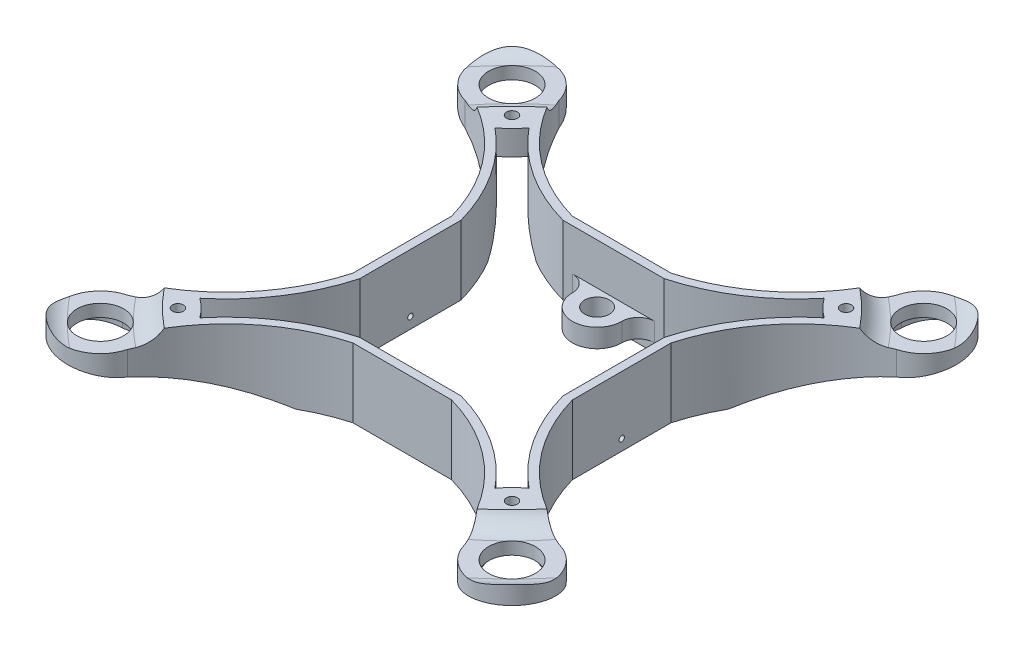
SolidWorks part; units mm, degrees
ref_plane "前视基准面" through (0, 0, 0) normal (0, 0, 1) x (1, 0, 0)
ref_plane "上视基准面" through (0, 0, 0) normal (0, 1, 0) x (1, 0, 0)
ref_plane "右视基准面" through (0, 0, 0) normal (1, 0, 0) x (0, 0, -1)
other "Configuration Table"
sketch "草图1" plane through (0, 0, 0) normal (0, 1, 0) x (1, 0, 0)
  line L5 (0, 0) -> (0, 44.9751) construction
  line L6 (0, 0) -> (70.3085, 0) construction
  line L11 (-18.5, 9.2045) -> (-18.5, -9.2045)
  line L17 (-20, -20) -> (20, 20) construction
  line L18 (-20, 20) -> (20, -20) construction
  line L23 (-37.5, -37.5) -> (37.5, 37.5) construction
  line L24 (-37.5, 37.5) -> (37.5, -37.5) construction
  line L25 (-9.2045, 18.5) -> (9.2045, 18.5)
  line L26 (-37.5, -37.5) -> (-32.5503, -32.5503)
  line L27 (-20, 9) -> (-20, -9)
  line L28 (0, 0) -> (32.5503, 32.5503)
  line L29 (18.5, 9.2045) -> (18.5, -9.2045)
  line L30 (9, -20) -> (-9, -20)
  line L31 (9.2045, -18.5) -> (-9.2045, -18.5)
  line L32 (20, 9) -> (20, -9)
  line L33 (-9, 20) -> (9, 20)
  arc A33 (-39.3117, -30.7385) -> (-30.7385, -39.3117) centre (-37.5, -37.5) ccw
  arc A34 (-30.7385, 39.3117) -> (-39.3117, 30.7385) centre (-37.5, 37.5) ccw
  circle A35 centre (-37.5, 37.5) radius 4.25
  circle A36 centre (37.5, 37.5) radius 4.25
  circle A37 centre (37.5, -37.5) radius 4.25
  circle A38 centre (-37.5, -37.5) radius 4.25
  arc A45 (30.7385, -39.3117) -> (39.3117, -30.7385) centre (37.5, -37.5) ccw
  arc A46 (39.3117, 30.7385) -> (30.7385, 39.3117) centre (37.5, 37.5) ccw
  arc A48 (-20, 9) -> (-39.3117, 30.7385) centre (-52.022, 0) ccw
  arc A51 (-39.3117, -30.7385) -> (-20, -9) centre (-52.022, 0) ccw
  arc A52 (-30.7385, 39.3117) -> (-9, 20) centre (0, 52.022) ccw
  arc A53 (9, 20) -> (30.7385, 39.3117) centre (0, 52.022) ccw
  arc A54 (20, -9) -> (39.3117, -30.7385) centre (52.022, 0) ccw
  arc A55 (39.3117, 30.7385) -> (20, 9) centre (52.022, 0) ccw
  arc A58 (30.7385, -39.3117) -> (9, -20) centre (0, -52.022) ccw
  arc A59 (-9, -20) -> (-30.7385, -39.3117) centre (0, -52.022) ccw
  arc A60 (-38.8355, -32.1646) -> (-18.5, -9.2045) centre (-52.022, 0) ccw
  arc A61 (-18.5, 9.2045) -> (-38.8355, 32.1646) centre (-52.022, 0) ccw
  arc A62 (-32.1646, 38.8355) -> (-38.8355, 32.1646) centre (-37.5, 37.5) ccw
  arc A63 (-32.1646, 38.8355) -> (-9.2045, 18.5) centre (0, 52.022) ccw
  arc A64 (9.2045, 18.5) -> (32.1646, 38.8355) centre (0, 52.022) ccw
  arc A65 (38.8355, 32.1646) -> (32.1646, 38.8355) centre (37.5, 37.5) ccw
  arc A66 (38.8355, 32.1646) -> (18.5, 9.2045) centre (52.022, 0) ccw
  arc A67 (18.5, -9.2045) -> (38.8355, -32.1646) centre (52.022, 0) ccw
  arc A68 (32.1646, -38.8355) -> (38.8355, -32.1646) centre (37.5, -37.5) ccw
  arc A69 (32.1646, -38.8355) -> (9.2045, -18.5) centre (0, -52.022) ccw
  arc A70 (-9.2045, -18.5) -> (-32.1646, -38.8355) centre (0, -52.022) ccw
  arc A71 (-38.8355, -32.1646) -> (-32.1646, -38.8355) centre (-37.5, -37.5) ccw
  point P3 (0, 0)
  point P9 (0, 0)
  dimension "D1" = 1.5
extrude "凸台-拉伸1" add sketch "草图1" along normal blind 12.6 contours A59 L30 A58 A45 A54 L32 A55 A46 A53 L33 A52 A34 A48 L27 A51 A33 A71 A60 L11 A61 A62 A63 L25 A64 A65 A66 L29 A67 A68 A69 L31 A70
sketch "草图3" plane through (0, 0, 0) normal (0, -1, 0) x (1, 0, 0)
  line L0 (-37.5, 37.5) -> (37.5, -37.5) construction
  line L2 (37.5, 37.5) -> (-37.5, -37.5) construction
ref_plane "基准面1" through (0, 0, 0) normal (0.7071, 0, -0.7071) x (-0.7071, 0, -0.7071)
ref_plane "基准面2" through (0, 0, 0) normal (-0.7071, 0, -0.7071) x (-0.7071, 0, 0.7071)
sketch "草图6" plane through (0, 12.6, 0) normal (0, 1, 0) x (1, 0, 0)
  line L0 (-37.5, 37.5) -> (-30.4289, 30.4289)
  line L1 (37.5, -37.5) -> (-37.5, 37.5) construction
  line L2 (-37.5, -37.5) -> (-30.4289, -30.4289)
  line L3 (-37.5, -37.5) -> (37.5, 37.5) construction
  line L4 (37.5, -37.5) -> (30.4289, -30.4289)
  line L5 (37.5, 37.5) -> (30.4289, 30.4289)
  arc A0 (-30.7385, 39.3117) -> (-39.3117, 30.7385) centre (-37.5, 37.5) ccw
  circle A1 centre (-37.5, 37.5) radius 4.25
  arc A2 (39.3117, 30.7385) -> (30.7385, 39.3117) centre (37.5, 37.5) ccw
  circle A3 centre (37.5, 37.5) radius 4.25
  arc A4 (30.7385, -39.3117) -> (39.3117, -30.7385) centre (37.5, -37.5) ccw
  circle A5 centre (37.5, -37.5) radius 4.25
  arc A6 (-39.3117, -30.7385) -> (-30.7385, -39.3117) centre (-37.5, -37.5) ccw
  circle A7 centre (-37.5, -37.5) radius 4.25
  circle A8 centre (-30.4289, 30.4289) radius 1
  arc A9 (-31.3407, 26.0517) -> (-26.0517, 31.3407) centre (-37.5, 37.5) ccw
  arc A10 (26.0517, 31.3407) -> (31.3407, 26.0517) centre (37.5, 37.5) ccw
  arc A11 (31.3407, -26.0517) -> (26.0517, -31.3407) centre (37.5, -37.5) ccw
  arc A12 (-26.0517, -31.3407) -> (-31.3407, -26.0517) centre (-37.5, -37.5) ccw
  circle A13 centre (-30.4289, -30.4289) radius 1
  circle A14 centre (30.4289, -30.4289) radius 1
  circle A15 centre (30.4289, 30.4289) radius 1
  arc A16 (20, -9) -> (39.3117, -30.7385) centre (52.022, 0) ccw construction
  arc A17 (30.7385, -39.3117) -> (9, -20) centre (0, -52.022) ccw construction
  arc A18 (-9, -20) -> (-30.7385, -39.3117) centre (0, -52.022) ccw construction
  arc A19 (-39.3117, -30.7385) -> (-20, -9) centre (-52.022, 0) ccw construction
  arc A20 (39.3117, 30.7385) -> (20, 9) centre (52.022, 0) ccw construction
  arc A21 (9, 20) -> (30.7385, 39.3117) centre (0, 52.022) ccw construction
  arc A22 (-20, 9) -> (-39.3117, 30.7385) centre (-52.022, 0) ccw construction
  arc A23 (-30.7385, 39.3117) -> (-9, 20) centre (0, 52.022) ccw construction
  arc A24 (31.3407, -26.0517) -> (39.3117, -30.7385) centre (52.022, 0) ccw
  arc A25 (30.7385, -39.3117) -> (26.0517, -31.3407) centre (0, -52.022) ccw
  arc A26 (-26.0517, -31.3407) -> (-30.7385, -39.3117) centre (0, -52.022) ccw
  arc A27 (-39.3117, -30.7385) -> (-31.3407, -26.0517) centre (-52.022, 0) ccw
  arc A28 (39.3117, 30.7385) -> (31.3407, 26.0517) centre (52.022, 0) ccw
  arc A29 (26.0517, 31.3407) -> (30.7385, 39.3117) centre (0, 52.022) ccw
  arc A30 (-31.3407, 26.0517) -> (-39.3117, 30.7385) centre (-52.022, 0) ccw
  arc A31 (-30.7385, 39.3117) -> (-26.0517, 31.3407) centre (0, 52.022) ccw
extrude "凸台-拉伸2" add sketch "草图6" against normal blind 4.5
sketch "草图4" plane through (0, 0, 0) normal (-0.7071, 0, -0.7071) x (-0.7071, 0, 0.7071)
  line L0 (0, 0) -> (0, 41.1063) construction
  line L2 (-49.533, 12.6) -> (-60.033, 12.6) construction
  line L3 (-53.033, 12.6) -> (-61.033, 12.6)
  line L4 (-53.033, 12.6) -> (-45.033, 12.6)
  line L6 (-53.033, 10.35) -> (-48.783, 10.35)
  line L7 (-53.033, 10.35) -> (-57.283, 10.35)
  arc A1 (-61.033, 12.6) -> (-56.783, 10.35) centre (-57.033, 15.0167) ccw
  arc A2 (-49.283, 10.35) -> (-45.033, 12.6) centre (-49.033, 15.0167) ccw
revolve "切除-旋转1" cut sketch "草图4" angle 360 about L0
sketch "草图7" plane through (0, 0, 0) normal (0.7071, 0, -0.7071) x (-0.7071, 0, -0.7071)
  line L0 (0, 0) -> (0, 23.5599) construction
  line L6 (-53.033, 0) -> (-60.033, 0)
  line L7 (-60.033, 0) -> (-60.033, 8.1)
  line L8 (-53.033, 0) -> (-28.28, 0)
  arc A1 (-28.28, 0) -> (-60.033, 8.1) centre (-104.9845, -234.4035) ccw
revolve "切除-旋转6" cut sketch "草图7" angle 360 about L0
sketch "草图10" plane through (0, 0, 0) normal (0, -1, 0) x (1, 0, 0)
  line L0 (18.5, 9.2045) -> (18.5, -9.2045) construction
  line L1 (20, -9) -> (20, 9) construction
  line L2 (-9, -20) -> (9, -20) construction
  line L4 (-18.5, -9.2045) -> (-18.5, 9.2045) construction
  line L5 (-20, 9) -> (-20, -9) construction
  line L6 (-9.2045, 18.5) -> (9.2045, 18.5) construction
  line L7 (9, 20) -> (-9, 20) construction
  line L8 (18.5, 9.2045) -> (18.5, -9.2045)
  line L9 (20, -9) -> (20, 9)
  line L10 (-9, -20) -> (9, -20)
  line L12 (-18.5, -9.2045) -> (-18.5, 9.2045)
  line L13 (-20, 9) -> (-20, -9)
  line L14 (-9.2045, 18.5) -> (9.2045, 18.5)
  line L15 (9, 20) -> (-9, 20)
  line L21 (0, -18.5) -> (4.5, -18.5)
  line L22 (0, -18.5) -> (-4.5, -18.5)
  line L23 (-4.5, -18.5) -> (-4.5, -15.5)
  line L24 (4.5, -18.5) -> (4.5, -15.5)
  arc A1 (22.083, 17.6664) -> (18.5, 9.2045) centre (52.022, 0) ccw construction
  arc A2 (18.5, -9.2045) -> (22.083, -17.6664) centre (52.022, 0) ccw construction
  arc A3 (4.5, -15.5) -> (-4.5, -15.5) centre (0, -15.5) ccw
  arc A4 (20, -9) -> (23.0637, -16.3653) centre (52.022, 0) ccw construction
  arc A5 (23.0637, 16.3653) -> (20, 9) centre (52.022, 0) ccw construction
  arc A7 (-9, -20) -> (-16.3653, -23.0637) centre (0, -52.022) ccw construction
  arc A8 (16.3653, -23.0637) -> (9, -20) centre (0, -52.022) ccw construction
  arc A10 (17.6664, -22.083) -> (9.2045, -18.5) centre (0, -52.022) ccw construction
  arc A11 (-9.2045, -18.5) -> (-17.6664, -22.083) centre (0, -52.022) ccw construction
  arc A13 (-22.083, -17.6664) -> (-18.5, -9.2045) centre (-52.022, 0) ccw construction
  arc A14 (-18.5, 9.2045) -> (-22.083, 17.6664) centre (-52.022, 0) ccw construction
  arc A16 (-20, 9) -> (-23.0637, 16.3653) centre (-52.022, 0) ccw construction
  arc A17 (-23.0637, -16.3653) -> (-20, -9) centre (-52.022, 0) ccw construction
  arc A19 (-17.6664, 22.083) -> (-9.2045, 18.5) centre (0, 52.022) ccw construction
  arc A20 (9.2045, 18.5) -> (17.6664, 22.083) centre (0, 52.022) ccw construction
  arc A22 (9, 20) -> (16.3653, 23.0637) centre (0, 52.022) ccw construction
  arc A23 (-16.3653, 23.0637) -> (-9, 20) centre (0, 52.022) ccw construction
  arc A25 (22.083, 17.6664) -> (18.5, 9.2045) centre (52.022, 0) ccw
  arc A26 (18.5, -9.2045) -> (22.083, -17.6664) centre (52.022, 0) ccw
  arc A28 (20, -9) -> (23.0637, -16.3653) centre (52.022, 0) ccw
  arc A29 (23.0637, 16.3653) -> (20, 9) centre (52.022, 0) ccw
  arc A31 (-9, -20) -> (-16.3653, -23.0637) centre (0, -52.022) ccw
  arc A32 (16.3653, -23.0637) -> (9, -20) centre (0, -52.022) ccw
  arc A34 (17.6664, -22.083) -> (9.2045, -18.5) centre (0, -52.022) ccw
  arc A35 (-9.2045, -18.5) -> (-17.6664, -22.083) centre (0, -52.022) ccw
  arc A37 (-22.083, -17.6664) -> (-18.5, -9.2045) centre (-52.022, 0) ccw
  arc A38 (-18.5, 9.2045) -> (-22.083, 17.6664) centre (-52.022, 0) ccw
  arc A40 (-20, 9) -> (-23.0637, 16.3653) centre (-52.022, 0) ccw
  arc A41 (-23.0637, -16.3653) -> (-20, -9) centre (-52.022, 0) ccw
  arc A43 (-17.6664, 22.083) -> (-9.2045, 18.5) centre (0, 52.022) ccw
  arc A44 (9.2045, 18.5) -> (17.6664, 22.083) centre (0, 52.022) ccw
  arc A46 (9, 20) -> (16.3653, 23.0637) centre (0, 52.022) ccw
  arc A47 (-16.3653, 23.0637) -> (-9, 20) centre (0, 52.022) ccw
  arc A48 (-16.3653, 23.0637) -> (-23.0637, 16.3653) centre (0, 0) ccw
  arc A49 (-23.0637, -16.3653) -> (-16.3653, -23.0637) centre (0, 0) ccw
  arc A50 (16.3653, -23.0637) -> (23.0637, -16.3653) centre (0, 0) ccw
  arc A51 (23.0637, 16.3653) -> (16.3653, 23.0637) centre (0, 0) ccw
  circle A52 centre (0, -15.5) radius 2.25
extrude "凸台-拉伸3" add sketch "草图10" against normal blind 5 contours L24 A3 L23 L22 L21 A52
sketch "草图11" plane through (0, 0, 0) normal (0, -1, 0) x (1, 0, 0)
  line L0 (-4.5, -18.5) -> (4.5, -18.5)
  line L5 (-9, -20) -> (9, -20)
  line L6 (9.2045, -18.5) -> (4.5, -18.5)
  line L7 (4.5, -18.5) -> (4.5, -15.5)
  line L8 (-4.5, -15.5) -> (-4.5, -18.5)
  line L9 (-4.5, -18.5) -> (-9.2045, -18.5)
  line L12 (4.5, -18.5) -> (4.5, -15.5)
  line L13 (-4.5, -15.5) -> (-4.5, -18.5)
  arc A7 (-17.6664, -22.083) -> (-16.3653, -23.0637) centre (0, 0) ccw
  arc A8 (-9, -20) -> (-16.3653, -23.0637) centre (0, -52.022) ccw
  arc A9 (16.3653, -23.0637) -> (9, -20) centre (0, -52.022) ccw
  arc A10 (16.3653, -23.0637) -> (17.6664, -22.083) centre (0, 0) ccw
  arc A11 (17.6664, -22.083) -> (9.2045, -18.5) centre (0, -52.022) ccw
  arc A12 (4.5, -15.5) -> (-4.5, -15.5) centre (0, -15.5) ccw
  arc A13 (-9.2045, -18.5) -> (-17.6664, -22.083) centre (0, -52.022) ccw
  arc A19 (4.5, -15.5) -> (-4.5, -15.5) centre (0, -15.5) ccw
  dimension "D1" = 0
extrude "切除-拉伸1" cut sketch "草图11" against normal blind 1.6
sketch "草图12" plane through (-20, 0, 0) normal (-1, 0, 0) x (0, 0, 1)
  circle A0 centre (0, 2) radius 0.5
extrude "切除-拉伸2" cut sketch "草图12" against normal blind 63.6
fillet "圆角1" radius 3 2 edges at (4.5, 3.3, -18.5) (-4.5, 3.3, -18.5)
